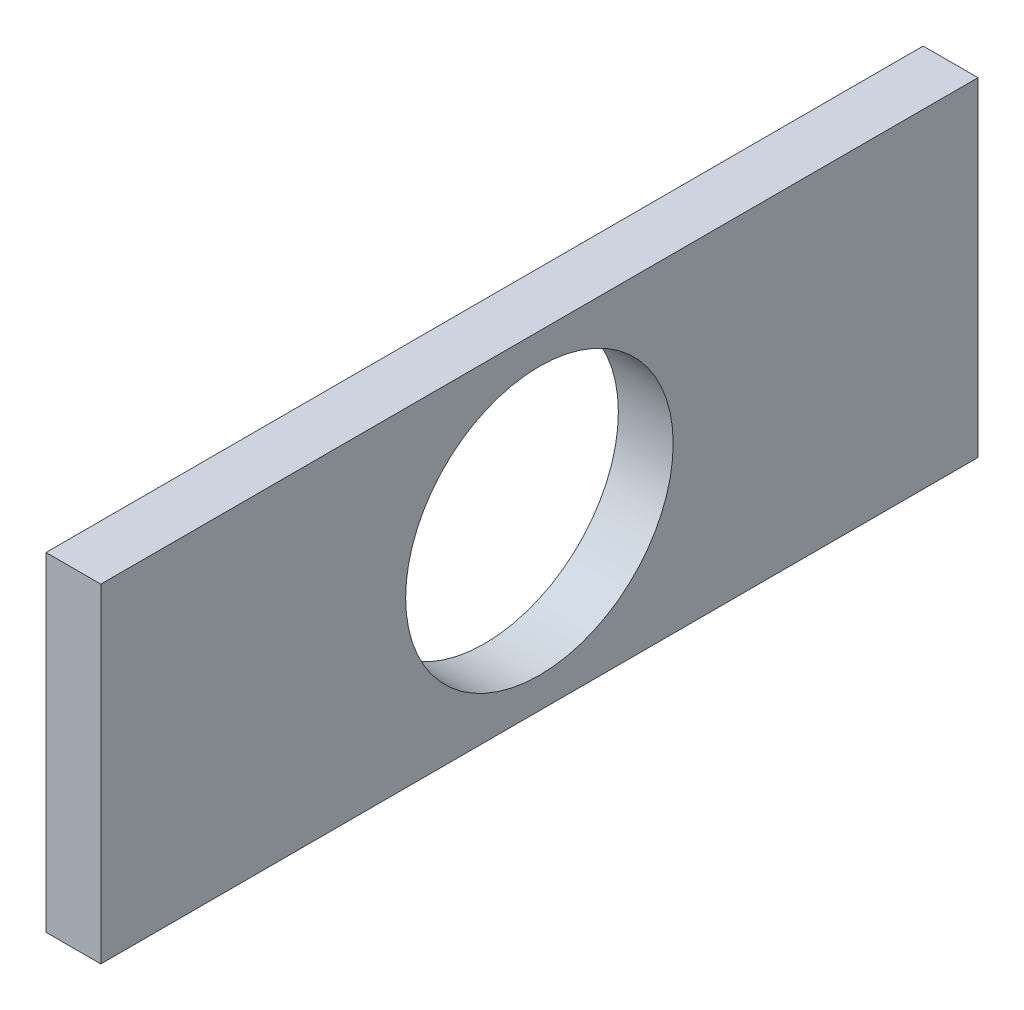
SolidWorks part; units mm, degrees
ref_plane "Front Plane" through (0, 0, 0) normal (0, 0, 1) x (1, 0, 0)
ref_plane "Top Plane" through (0, 0, 0) normal (0, 1, 0) x (1, 0, 0)
ref_plane "Right Plane" through (0, 0, 0) normal (1, 0, 0) x (0, 0, -1)
sketch "Sketch1" plane through (0, 0, 0) normal (1, 0, 0) x (0, 0, -1)
  line L1 (-50.8, -19.05) -> (50.8, -19.05)
  line L2 (-50.8, -19.05) -> (-50.8, 19.05)
  line L3 (-50.8, 19.05) -> (50.8, 19.05)
  line L4 (50.8, -19.05) -> (50.8, 19.05)
  line L5 (-50.8, -19.05) -> (50.8, 19.05) construction
  line L6 (-50.8, 19.05) -> (50.8, -19.05) construction
  circle A0 centre (0, 0) radius 15.494
  point P0 (0, 0)
  dimension "D3" = 30.988
  dimension "D1" = 101.6
  dimension "D2" = 38.1
extrude "Boss-Extrude1" add sketch "Sketch1" along normal blind 6.35
